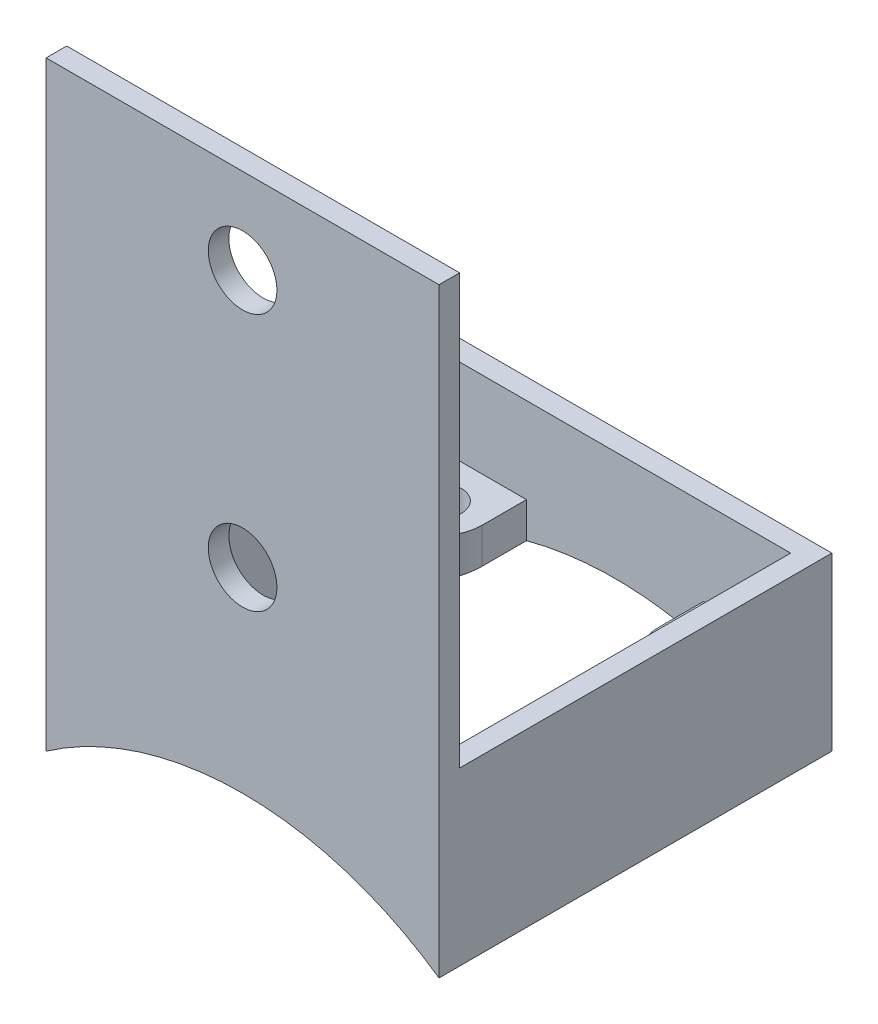
SolidWorks part; units mm, degrees
ref_plane "前视基准面" through (0, 0, 0) normal (0, 0, 1) x (1, 0, 0)
ref_plane "上视基准面" through (0, 0, 0) normal (0, 1, 0) x (1, 0, 0)
ref_plane "右视基准面" through (0, 0, 0) normal (1, 0, 0) x (0, 0, -1)
sketch "草图1" plane through (0, 0, 0) normal (0, 1, 0) x (1, 0, 0)
  line L0 (0, -1000) -> (0, 49000) construction
  line L1 (-10.25, 10.25) -> (10.25, 10.25)
  line L2 (-10.25, 10.25) -> (-10.25, -10.25)
  line L3 (-10.25, -10.25) -> (10.25, -10.25)
  line L4 (10.25, 10.25) -> (10.25, -10.25)
  line L5 (-10.25, 10.25) -> (10.25, -10.25) construction
  line L6 (-10.25, -10.25) -> (10.25, 10.25) construction
  line L7 (-5.15, 7.65) -> (-5.15, 10.25)
  line L8 (-11.45, 11.45) -> (11.45, 11.45)
  line L9 (-11.45, 11.45) -> (-11.45, -11.45)
  line L10 (-11.45, -11.45) -> (11.45, -11.45)
  line L11 (11.45, 11.45) -> (11.45, -11.45)
  line L12 (-11.45, 11.45) -> (11.45, -11.45) construction
  line L13 (-11.45, -11.45) -> (11.45, 11.45) construction
  line L14 (-7.62, 5.18) -> (-10.25, 5.18)
  line L15 (5.15, 7.65) -> (5.15, 10.25)
  line L16 (-10.25, 10.25) -> (-10.25, -10.25)
  line L17 (10.25, 10.25) -> (10.25, -10.25)
  line L18 (7.62, 5.18) -> (10.25, 5.18)
  line L19 (-10.25, -10.25) -> (-11.45, -10.25)
  line L20 (10.25, -10.25) -> (11.45, -10.25)
  circle A1 centre (-7.62, 7.65) radius 1.27
  arc A3 (-7.62, 5.18) -> (-5.15, 7.65) centre (-7.62, 7.65) ccw
  arc A4 (-5.15, 7.65) -> (-9.3815, 9.3815) centre (-7.62, 7.65) ccw construction
  arc A5 (-9.3815, 9.3815) -> (-7.62, 5.18) centre (-7.62, 7.65) ccw construction
  arc A6 (7.62, 5.18) -> (5.15, 7.65) centre (7.62, 7.65) cw
  circle A7 centre (7.62, 7.65) radius 1.27
  arc A8 (9.3815, 9.3815) -> (7.62, 5.18) centre (7.62, 7.65) cw construction
  arc A9 (5.15, 7.65) -> (9.3815, 9.3815) centre (7.62, 7.65) cw construction
  point P0 (0, 0)
  point P12 (0, 0)
  dimension "D3" = 2.54
  dimension "D4" = 15.24
  dimension "D5" = 2.6
  dimension "D8" = 1.2
  dimension "D1" = 20.5
  dimension "D2" = 20.5
  dimension "D6" = 1.2
  dimension "D7" = 1.2
extrude "凸台-拉伸1" add sketch "草图1" along normal blind 10 contours L11 L8 L9 L10 L1 L4 L17 L3 L2 | L20 L3 L19 L9 L10 L11 region at (-10.5655, 0, -7.715) region at (0, 0, 10.85)
extrude "凸台-拉伸2" add sketch "草图1<4>" along normal blind 5 contours L14 A3 L7 L1 L2 A1 | A6 L18 L4 L1 L15 A7 region at (-7.7, 0, -10.1781) region at (7.7, 0, -10.1781)
sketch "草图1<4>" plane through (0, 0, 0) normal (0, 1, 0) x (1, 0, 0) same geometry as "草图1"
extrude "凸台-拉伸3" add sketch "草图1<5>" along normal blind 10 contours L20 L3 L19 L9 L10 L11 region at (0, 0, 10.85)
sketch "草图1<5>" plane through (0, 0, 0) normal (0, 1, 0) x (1, 0, 0) same geometry as "草图1"
sketch "草图3" plane through (0, 10, 0) normal (0, 1, 0) x (1, 0, 0)
  line L0 (-11.45, 11.45) -> (-11.45, -11.45) construction
  line L1 (-11.45, -10.25) -> (11.45, -10.25)
  line L2 (-11.45, -10.25) -> (-11.45, -11.45)
  line L3 (-11.45, -11.45) -> (11.45, -11.45)
  line L4 (11.45, -10.25) -> (11.45, -11.45)
extrude "凸台-拉伸4" add sketch "草图3" along normal blind 25
sketch "草图4" plane through (0, 0, -11.45) normal (0, 0, -1) x (-1, 0, 0)
  circle A0 centre (0, -16.3981) radius 20
  dimension "D1" = 40
extrude "切除-拉伸1" cut sketch "草图4" against normal up to next
sketch "草图5" plane through (0, 0, 10.25) normal (0, 0, -1) x (-1, 0, 0)
  line L1 (-11.45, 35) -> (11.45, 35) construction
  circle A0 centre (0, 15) radius 2
  circle A1 centre (0, 30) radius 2
  point P9 (0, 35)
  dimension "D1" = 4
  dimension "D2" = 4
  dimension "D4" = 15
  dimension "D3" = 5
extrude "切除-拉伸2" cut sketch "草图5" against normal through all
